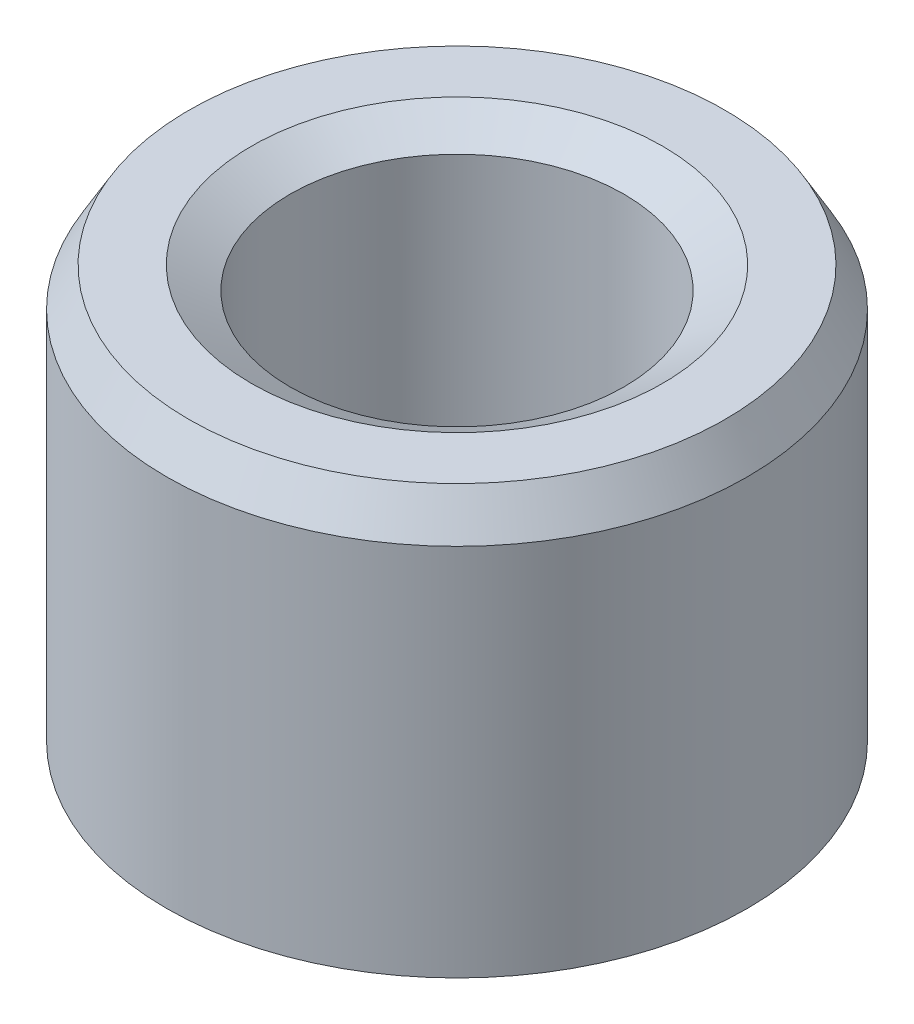
SolidWorks part; units mm, degrees
ref_plane "Front Plane" through (0, 0, 0) normal (0, 0, 1) x (1, 0, 0)
ref_plane "Top Plane" through (0, 0, 0) normal (0, 1, 0) x (1, 0, 0)
ref_plane "Right Plane" through (0, 0, 0) normal (1, 0, 0) x (0, 0, -1)
sketch "Sketch1" plane through (0, 0, 0) normal (0, 1, 0) x (1, 0, 0)
  circle A0 centre (0, 0) radius 17.5
  dimension "SLEEVE_OD" = 35
extrude "Boss-Extrude1" add sketch "Sketch1" along normal blind 26.2063
sketch "Sketch2" plane through (0, 0, 0) normal (0, 1, 0) x (1, 0, 0)
  circle A0 centre (0, 0) radius 10.0671
  dimension "BORE_D" = 20.1342
extrude "Cut-Extrude1" cut sketch "Sketch2" along normal through all
chamfer "Chamfer1" distance 2.3269 angle 30 4 edges at (0, 26.2063, 10.0671) (0, 0, 10.0671) (0, 0, 17.5) (0, 26.2063, 17.5) first distance on face at (0, 26.2063, 10.0671) first distance on face at (0, 0, 10.0671) first distance on face at (0, 26.2063, 17.5)
